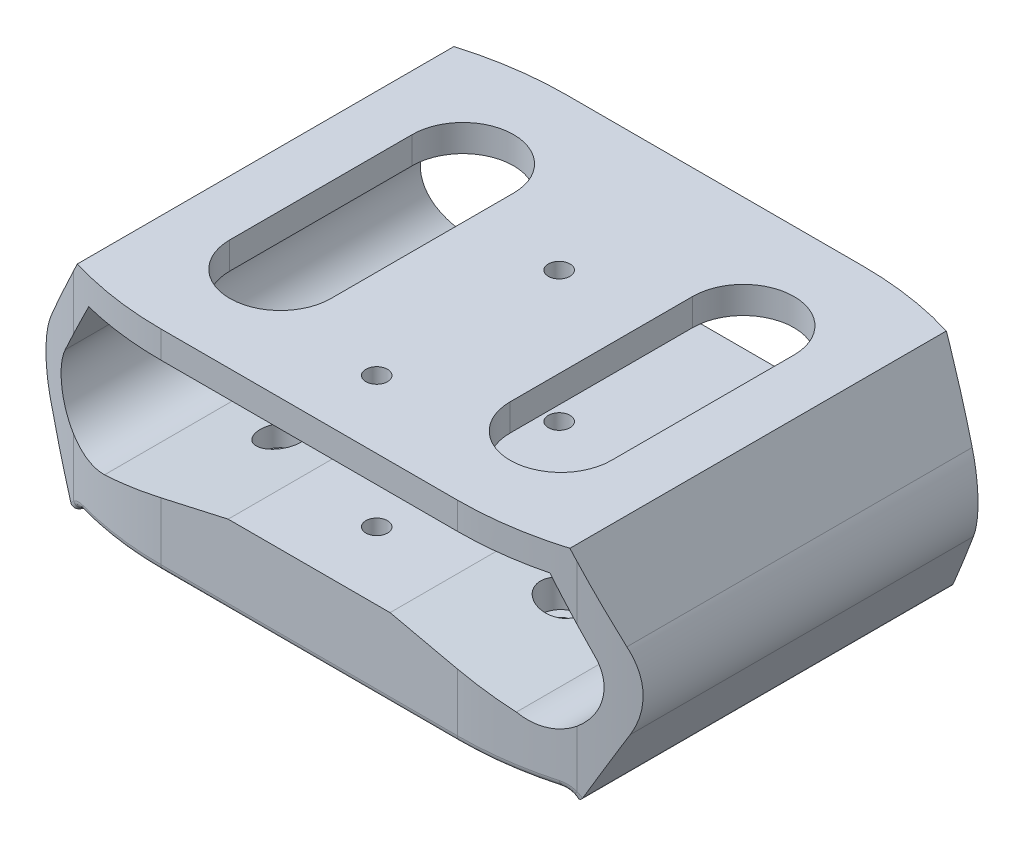
SolidWorks part; units mm, degrees
ref_plane "前视基准面" through (0, 0, 0) normal (0, 0, 1) x (1, 0, 0)
ref_plane "上视基准面" through (0, 0, 0) normal (0, 1, 0) x (1, 0, 0)
ref_plane "右视基准面" through (0, 0, 0) normal (1, 0, 0) x (0, 0, -1)
sketch "草图1" plane through (0, 0, 0) normal (0, 0, 1) x (1, 0, 0)
  line L6 (-36.4384, 98.3864) -> (-42.625, 87.564)
  line L10 (42.5656, 87.668) -> (36.4384, 98.3864)
  line L11 (36.4384, 98.3864) -> (-36.4384, 98.3864)
  line L12 (-34.1176, 94.3864) -> (-39.1524, 85.5789)
  line L13 (-31.105, 74.6866) -> (-11.9778, 78.9864)
  line L14 (-11.9778, 78.9864) -> (11.9778, 78.9864)
  line L15 (11.9778, 78.9864) -> (30.0087, 74.933)
  line L16 (39.118, 85.639) -> (34.1176, 94.3864)
  line L17 (34.1176, 94.3864) -> (-34.1176, 94.3864)
  line L18 (-34.1176, 94.3864) -> (-39.1524, 85.5789)
  line L19 (-31.105, 74.6866) -> (-11.9778, 78.9864)
  line L20 (-11.9778, 78.9864) -> (11.9778, 78.9864)
  line L21 (11.9778, 78.9864) -> (30.0087, 74.933)
  line L22 (39.118, 85.639) -> (34.1176, 94.3864)
  line L23 (34.1176, 94.3864) -> (-34.1176, 94.3864)
  line L24 (35, 67.1864) -> (21.943, 67.1864) construction
  line L25 (-21.943, 67.1864) -> (21.943, 67.1864) construction
  line L26 (-21.943, 67.1864) -> (-35, 67.1864) construction
  line L27 (35, 67.1864) -> (21.943, 67.1864)
  line L28 (-21.943, 67.1864) -> (21.943, 67.1864)
  line L29 (-21.943, 67.1864) -> (-35, 67.1864)
  line L30 (-37, 65.1864) -> (-42.8843, 76.7286)
  line L31 (37, 65.1864) -> (42.908, 76.5149)
  line L33 (-30.2277, 70.7839) -> (-11.5337, 74.9864) construction
  line L34 (-11.5337, 74.9864) -> (11.5337, 74.9864) construction
  line L35 (11.5337, 74.9864) -> (28.8425, 71.0953) construction
  arc A2 (-42.625, 87.564) -> (-42.8843, 76.7286) centre (-32.728, 81.9064) ccw
  arc A3 (42.908, 76.5149) -> (42.5656, 87.668) centre (32.8, 81.7864) ccw
  arc A4 (-39.1524, 85.5789) -> (-31.105, 74.6866) centre (-32.728, 81.9064) ccw
  arc A5 (30.0087, 74.933) -> (39.118, 85.639) centre (32.8, 81.7864) ccw
  arc A6 (-39.1524, 85.5789) -> (-31.105, 74.6866) centre (-32.728, 81.9064) ccw
  arc A7 (30.0087, 74.933) -> (39.118, 85.639) centre (32.8, 81.7864) ccw
  arc A8 (37, 65.1864) -> (35, 67.1864) centre (35, 65.1864) ccw construction
  arc A9 (-35, 67.1864) -> (-37, 65.1864) centre (-35, 65.1864) ccw construction
  arc A10 (37, 65.1864) -> (35, 67.1864) centre (35, 65.1864) ccw
  arc A11 (-35, 67.1864) -> (-37, 65.1864) centre (-35, 65.1864) ccw
  arc A12 (-42.625, 87.564) -> (-30.2277, 70.7839) centre (-32.728, 81.9064) ccw construction
  arc A13 (28.8425, 71.0953) -> (42.5656, 87.668) centre (32.8, 81.7864) ccw construction
  dimension "D1" = 0.2
  dimension "D2" = 4
extrude "凸台-拉伸1" add sketch "草图1" against normal up to surface (60 mm away)
sketch "草图2" plane through (0, 67.1864, 0) normal (0, -1, 0) x (1, 0, 0)
  line L1 (46.1297, -53.7608) -> (54.661, -49.0455) construction
  line L2 (46.1297, -53.7608) -> (54.661, -49.0455)
  line L3 (35, -60) -> (-35, -60) construction
  line L4 (21.943, -58) -> (21.943, -60) construction
  line L5 (54.661, -49.0455) -> (55.2201, -72.0519)
  line L6 (55.2201, -72.0519) -> (47.4236, -78.506)
  line L7 (47.4236, -78.506) -> (21.943, -68.9024)
  line L8 (21.943, -68.9024) -> (21.943, -60)
  line L12 (-47.4236, -78.506) -> (-21.943, -68.9024)
  line L13 (-55.2201, -72.0519) -> (-47.4236, -78.506)
  line L14 (-54.661, -49.0455) -> (-55.2201, -72.0519)
  line L15 (-46.1297, -53.7608) -> (-54.661, -49.0455)
  line L16 (-21.943, -68.9024) -> (-21.943, -60)
  line L19 (-55.2201, 12.0519) -> (-47.4236, 18.506)
  line L20 (-54.661, -10.9545) -> (-55.2201, 12.0519)
  line L21 (-46.1297, -6.2392) -> (-54.661, -10.9545)
  line L22 (-21.943, 8.9024) -> (-21.943, 0)
  line L23 (-47.4236, 18.506) -> (-21.943, 8.9024)
  line L24 (47.4236, 18.506) -> (21.943, 8.9024)
  line L25 (55.2201, 12.0519) -> (47.4236, 18.506)
  line L26 (54.661, -10.9545) -> (55.2201, 12.0519)
  line L27 (46.1297, -6.2392) -> (54.661, -10.9545)
  line L28 (21.943, 8.9024) -> (21.943, 0)
  arc A0 (37.2486, -57.5998) -> (21.943, -60) centre (21.943, -10) cw
  arc A1 (-37.2486, -57.5998) -> (-21.943, -60) centre (-21.943, -10) ccw
  arc A2 (-37.2486, -2.4002) -> (-21.943, 0) centre (-21.943, -50) cw
  arc A3 (37.2486, -2.4002) -> (21.943, 0) centre (21.943, -50) ccw
  spline S0 degree 3 poles (-1285.9943, 1433.6768) (-243.3632, -0.9152) (-26.08, -85.4419) (135.79, -14.9664) (-55.3237, 244.096) (509.0811, -1999.3449) knots -22.492359 -22.492359 -22.492359 -22.492359 0.5 0.5 32.253699 32.253699 32.253699 32.253699 only from (37.2486, -57.5998) to (46.1297, -53.7608) construction
  spline S1 degree 3 poles (37.2486, -57.5998) (38.8751, -57.0768) (40.4241, -56.4871) (43.3808, -55.1998) (44.7885, -54.502) (46.1297, -53.7608) knots 0 0 0 0 0.5 0.5 1 1 1 1
  spline S2 degree 3 poles (-37.2486, -57.5998) (-38.8751, -57.0768) (-40.4241, -56.4871) (-43.3808, -55.1998) (-44.7885, -54.502) (-46.1297, -53.7608) knots 0 0 0 0 0.5 0.5 1 1 1 1
  spline S3 degree 3 poles (-37.2486, -2.4002) (-38.8751, -2.9232) (-40.4241, -3.5129) (-43.3808, -4.8002) (-44.7885, -5.498) (-46.1297, -6.2392) knots 0 0 0 0 0.5 0.5 1 1 1 1
  spline S4 degree 3 poles (37.2486, -2.4002) (38.8751, -2.9232) (40.4241, -3.5129) (43.3808, -4.8002) (44.7885, -5.498) (46.1297, -6.2392) knots 0 0 0 0 0.5 0.5 1 1 1 1
extrude "切除-拉伸1" cut sketch "草图2" against normal mid plane 138
fillet "圆角1" radius 1 12 edges at (33.7286, 63.6425, -58.5912) (28.5289, 67.1864, -59.5644) (0, 67.1864, -60) (-36.4206, 66.5942, -57.8581) (33.5845, 63.7735, -1.3741) (28.5289, 67.1864, -0.4356) (0, 67.1864, 0) (-28.5289, 67.1864, -0.4356) (-28.5289, 67.1864, -59.5644) (37, 65.1864, -30) (-37, 65.1864, -30) (-36.7035, 66.2343, -2.2284)
sketch "草图4" plane through (0, 98.3864, 0) normal (0, 1, 0) x (1, 0, 0)
  line L0 (-20.7462, 43.5) -> (-20.7462, 16.5) construction
  line L1 (-13.2462, 43.5) -> (-13.2462, 16.5)
  line L2 (-28.2462, 43.5) -> (-28.2462, 16.5)
  line L3 (0, 66.5679) -> (0, 53.4321) construction
  line L4 (20.7462, 43.5) -> (20.7462, 16.5) construction
  line L5 (13.2462, 43.5) -> (13.2462, 16.5)
  line L6 (28.2462, 43.5) -> (28.2462, 16.5)
  arc A0 (-13.2462, 43.5) -> (-28.2462, 43.5) centre (-20.7462, 43.5) ccw
  arc A1 (-28.2462, 16.5) -> (-13.2462, 16.5) centre (-20.7462, 16.5) ccw
  arc A2 (13.2462, 43.5) -> (28.2462, 43.5) centre (20.7462, 43.5) cw
  arc A3 (28.2462, 16.5) -> (13.2462, 16.5) centre (20.7462, 16.5) cw
  point P4 (-20.7462, 30)
  point P13 (20.7462, 30)
extrude "切除-拉伸2" cut sketch "草图4" against normal blind 8
sketch "草图5" plane through (0, 98.3864, 0) normal (0, 1, 0) x (1, 0, 0)
  circle A0 centre (-20.7462, 43.5) radius 1.6
  circle A1 centre (-20.7462, 16.5) radius 1.6
  circle A2 centre (20.7462, 43.5) radius 1.6
  circle A3 centre (20.7462, 16.5) radius 1.6
extrude "切除-拉伸3" cut sketch "草图5" against normal blind 80
sketch "草图6" plane through (0, 98.3864, 0) normal (0, 1, 0) x (1, 0, 0)
  circle A0 centre (-20.7462, 43.5) radius 3
  circle A1 centre (20.7462, 43.5) radius 3
  circle A2 centre (-20.7462, 16.5) radius 3
  circle A3 centre (20.7462, 16.5) radius 3
extrude "切除-拉伸4" cut sketch "草图6" against normal blind 25
sketch "草图7" plane through (0, 98.3864, 0) normal (0, 1, 0) x (1, 0, 0)
  circle A0 centre (0, 37) radius 1.6
  circle A1 centre (0, 10) radius 1.6
extrude "切除-拉伸5" cut sketch "草图7" against normal blind 36
